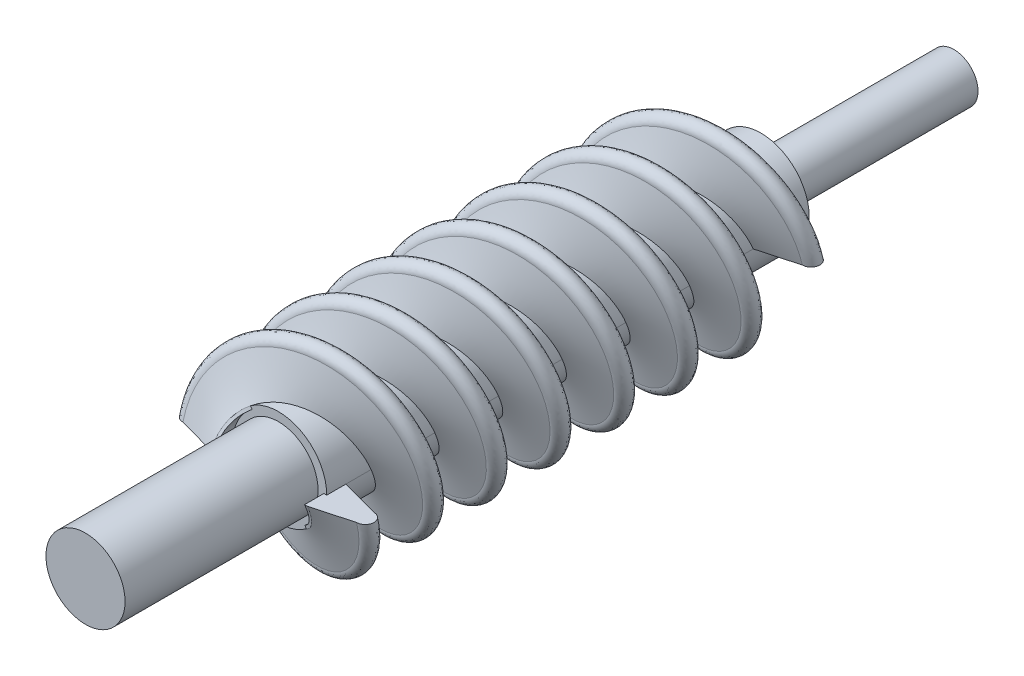
SolidWorks part; units mm, degrees
ref_plane "Plan de face" through (0, 0, 0) normal (0, 0, 1) x (1, 0, 0)
ref_plane "Plan de dessus" through (0, 0, 0) normal (0, 1, 0) x (1, 0, 0)
ref_plane "Plan de droite" through (0, 0, 0) normal (1, 0, 0) x (0, 0, -1)
sketch "Esquisse1" plane through (0, 0, 0) normal (0, 0, 1) x (1, 0, 0)
  circle A0 centre (0, 0) radius 5
  dimension "D1" = 10
extrude "Boss.-Extru.1" add sketch "Esquisse1" along normal blind 50
sketch "Esquisse3" plane through (0, 0, 50) normal (0, 0, 1) x (1, 0, 0)
  circle A0 centre (0, 0) radius 5
curve "Hélice/Spirale1" pitch 13.2 height 46.2 radius 5 centre (0, 0, 50) axis (0, 0, -1) start towards (-1, 0, 0)
sketch "Esquisse4" plane through (0, 0, 0) normal (0, 1, 0) x (1, 0, 0)
  line L0 (-5, -50) -> (-9, -50) construction
  line L1 (-5, 0) -> (-5, -50) construction
  line L2 (-9, -49.1) -> (-5, -48)
  line L3 (-9, -50.9) -> (-5, -52)
  line L5 (-5, -48) -> (-4.702, -48)
  line L6 (-4.702, -48) -> (-4.702, -52)
  line L7 (-4.702, -52) -> (-5, -52)
  arc A1 (-9, -49.1) -> (-9, -50.9) centre (-9, -50) ccw
  spline S0 degree 3 poles (-5, -50) (-5, -49.7265) (-4.7397, -49.1743) (-3.6276, -48.3502) (-1.9632, -47.525) (0, -46.7) (1.9632, -45.875) (3.6276, -45.05) (4.7397, -44.225) (5.1302, -43.4) (4.7397, -42.575) (3.6276, -41.75) (1.4084, -40.65) (-1.4084, -39.55) (-3.6276, -38.45) (-4.7397, -37.625) (-5.1302, -36.8) (-4.7397, -35.975) (-3.6276, -35.15) (-1.4084, -34.05) (1.4084, -32.95) (3.6276, -31.85) (4.7397, -31.025) (5.1302, -30.2) (4.7397, -29.375) (3.6276, -28.55) (1.4084, -27.45) (-1.4084, -26.35) (-3.6276, -25.25) (-4.7397, -24.425) (-5.1302, -23.6) (-4.7397, -22.775) (-3.6276, -21.95) (-1.4084, -20.85) (1.4084, -19.75) (3.6276, -18.65) (4.7397, -17.825) (5.1302, -17) (4.7397, -16.175) (3.6276, -15.35) (1.4084, -14.25) (-1.4084, -13.15) (-3.6276, -12.05) (-4.7397, -11.225) (-5.1302, -10.4) (-4.7397, -9.575) (-3.6276, -8.75) (-1.9632, -7.925) (0, -7.1) (1.9632, -6.275) (3.6276, -5.4498) (4.7397, -4.6257) (5, -4.0735) (5, -3.8) knots 0 0 0 0 0.017857 0.035714 0.053571 0.071429 0.089286 0.107143 0.125 0.142857 0.160714 0.178571 0.196429 0.232143 0.25 0.267857 0.285714 0.303571 0.321429 0.339286 0.375 0.392857 0.410714 0.428571 0.446429 0.464286 0.482143 0.517857 0.535714 0.553571 0.571429 0.589286 0.607143 0.625 0.660714 0.678571 0.696429 0.714286 0.732143 0.75 0.767857 0.803571 0.821429 0.839286 0.857143 0.875 0.892857 0.910714 0.928571 0.946429 0.964286 0.982143 1 1 1 1 construction
  dimension "D3" = 0.9
  dimension "D1" = 4
  dimension "D2" = 4
sweep "Balayage2" add profiles "Esquisse4" path "Hélice/Spirale1"
pattern_circular "CirPattern1" count 2 over 360 about axis through (0, 0, 50) along (0, 0, -1) of "Balayage2"
sketch "arbre" plane through (0, 0, 0) normal (0, 0, -1) x (-1, 0, 0)
  circle A0 centre (0, 0) radius 2.5
extrude "Boss.-Extru.3" add sketch "arbre" along normal blind 20 and the other way blind 70
sketch "Esquisse8" plane through (0, 0, 70) normal (0, 0, 1) x (1, 0, 0)
  circle A0 centre (0, 0) radius 4.1
extrude "Boss.-Extru.4" add sketch "Esquisse8" against normal blind 20
